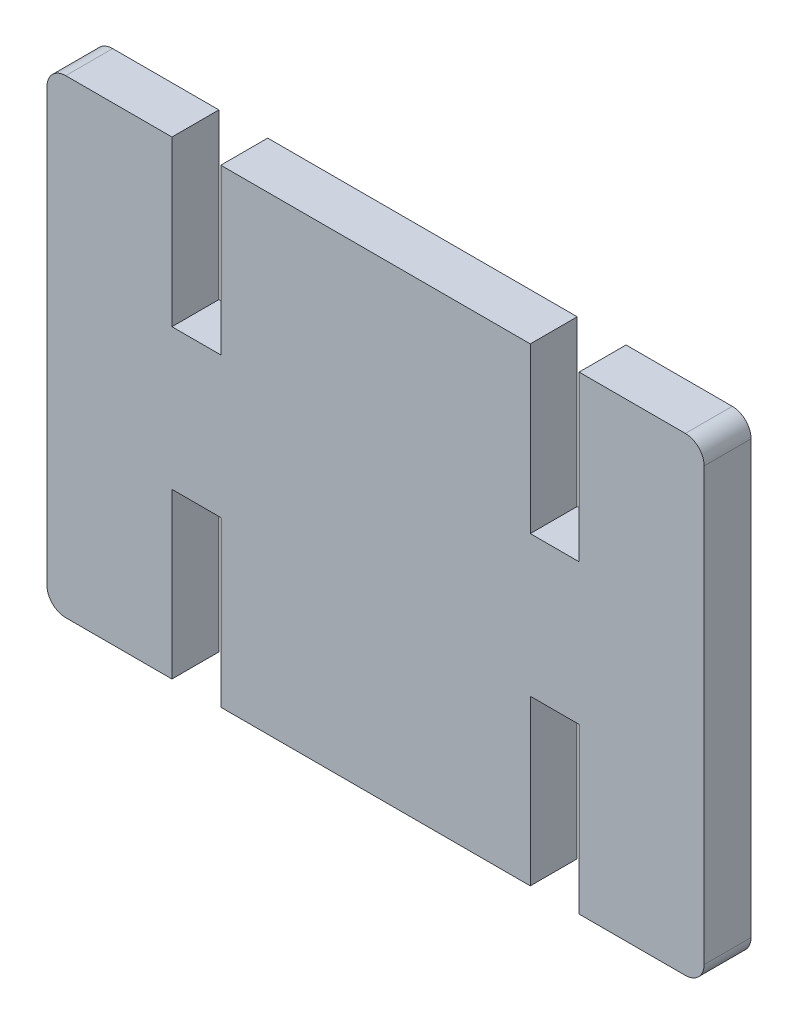
SolidWorks part; units mm, degrees
material "Acrylic (Medium-high impact)"
ref_plane "Front Plane" through (0, 0, 0) normal (0, 0, 1) x (1, 0, 0)
ref_plane "Top Plane" through (0, 0, 0) normal (0, 1, 0) x (1, 0, 0)
ref_plane "Right Plane" through (0, 0, 0) normal (1, 0, 0) x (0, 0, -1)
sketch "Sketch1" plane through (0, 0, 0) normal (0, 0, 1) x (1, 0, 0)
  line L0 (2, 0) -> (68, 0)
  line L1 (0, 2) -> (0, 48)
  line L2 (70, 2) -> (70, 48)
  line L3 (2, 50) -> (68, 50)
  arc A0 (70, 48) -> (68, 50) centre (68, 48) ccw
  arc A1 (0, 48) -> (2, 50) centre (2, 48) cw
  arc A2 (68, 0) -> (70, 2) centre (68, 2) ccw
  arc A3 (0, 2) -> (2, 0) centre (2, 2) ccw
  point P7 (70, 50)
  point P10 (0, 50)
  point P13 (70, 0)
  point P16 (0, 0)
  dimension "D3" = 2
  dimension "D1" = 70
  dimension "D2" = 50
extrude "Boss-Extrude1" add sketch "Sketch1" along normal blind 5
extrude "Cut-Extrude1" cut sketch "Sketch2" against normal blind 5
sketch "Sketch2" plane through (-23.3993, 94.9169, 5) normal (0, 0, 1) x (1, 0, 0)
  line L0 (36.7163, -62.4169) -> (36.7163, -44.9169)
  line L1 (91.3993, -44.9169) -> (25.3993, -44.9169) construction
  line L2 (36.7163, -44.9169) -> (41.9163, -44.9169)
  line L3 (41.9163, -44.9169) -> (41.9163, -62.4169)
  line L4 (36.7163, -62.4169) -> (41.9163, -62.4169)
  line L5 (74.8822, -62.4169) -> (74.8822, -44.9169)
  line L6 (74.8822, -44.9169) -> (80.0822, -44.9169)
  line L7 (80.0822, -44.9169) -> (80.0822, -62.4169)
  line L8 (80.0822, -62.4169) -> (74.8822, -62.4169)
  line L9 (77.4822, -44.9169) -> (77.4822, -62.4169) construction
  line L10 (39.3163, -44.9169) -> (39.3163, -62.4169) construction
  line L11 (58.3993, -44.9169) -> (58.3993, -94.9169) construction
  line L12 (25.3993, -94.9169) -> (91.3993, -94.9169) construction
  line L13 (36.7163, -94.9169) -> (36.7163, -77.4169)
  line L14 (36.7163, -94.9169) -> (41.9163, -94.9169)
  line L15 (36.7163, -77.4169) -> (41.9163, -77.4169)
  line L16 (41.9163, -94.9169) -> (41.9163, -77.4169)
  line L17 (74.8822, -94.9169) -> (74.8822, -77.4169)
  line L18 (74.8822, -94.9169) -> (80.0822, -94.9169)
  line L19 (74.8822, -77.4169) -> (80.0822, -77.4169)
  line L20 (80.0822, -94.9169) -> (80.0822, -77.4169)
  line L21 (23.3993, -69.9169) -> (93.3993, -69.9169) construction
  line L22 (23.3993, -46.9169) -> (23.3993, -92.9169) construction
  line L23 (93.3993, -92.9169) -> (93.3993, -46.9169) construction
  dimension "D1" = 5.2
  dimension "D3" = 38.1659
  dimension "D4" = 15
